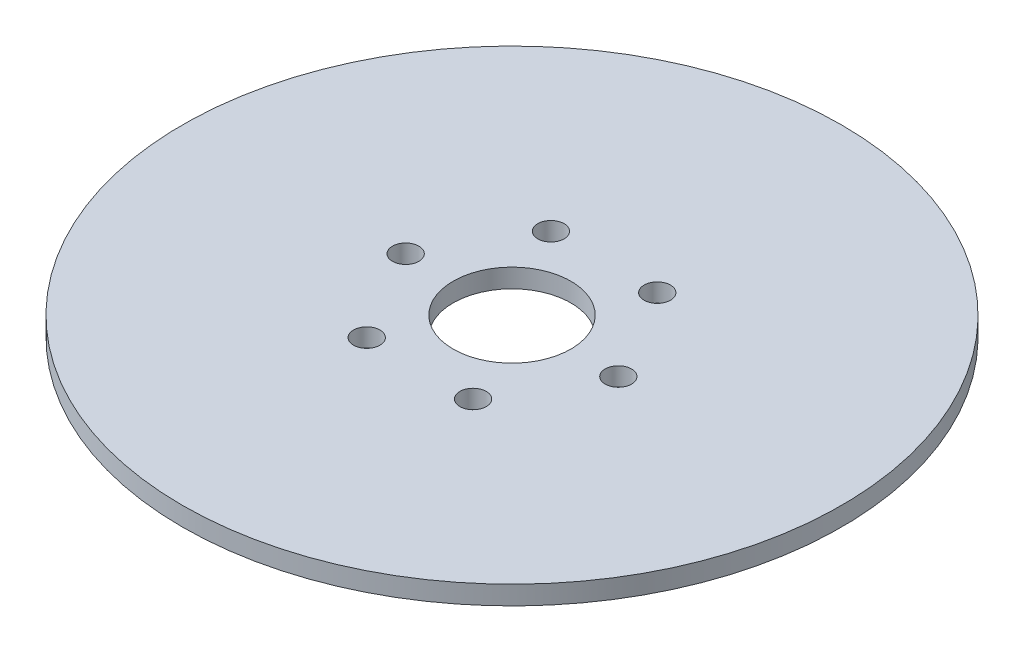
SolidWorks part; units mm, degrees
ref_plane "Front Plane" through (0, 0, 0) normal (0, 0, 1) x (1, 0, 0)
ref_plane "Top Plane" through (0, 0, 0) normal (0, 1, 0) x (1, 0, 0)
ref_plane "Right Plane" through (0, 0, 0) normal (1, 0, 0) x (0, 0, -1)
sketch "Sketch1" plane through (0, 0, 0) normal (0, 1, 0) x (1, 0, 0)
  circle A0 centre (0, 0) radius 70
  dimension "FLANGE_OD" = 140
extrude "Boss-Extrude1" add sketch "Sketch1" along normal blind 4
sketch "Sketch2" plane through (0, 0, 0) normal (0, 1, 0) x (1, 0, 0)
  circle A0 centre (0, 0) radius 12.5
  dimension "BORE_D" = 25
extrude "Cut-Extrude1" cut sketch "Sketch2" along normal through all
sketch "Sketch3" plane through (0, 4, 0) normal (0, 1, 0) x (1, 0, 0)
  circle A0 centre (0, 0) radius 22.5882 construction
  circle A1 centre (-22.5882, 0) radius 2.8016
  dimension "BOLT_D" = 5.6033
  dimension "BOLT_PCD" = 45.1763
extrude "Cut-Extrude2" cut sketch "Sketch3" against normal blind 3.918
pattern_circular "CirPattern1" count 6 over 360 about axis through (0, 0, 0) along (0, 1, 0) of "Cut-Extrude2"
